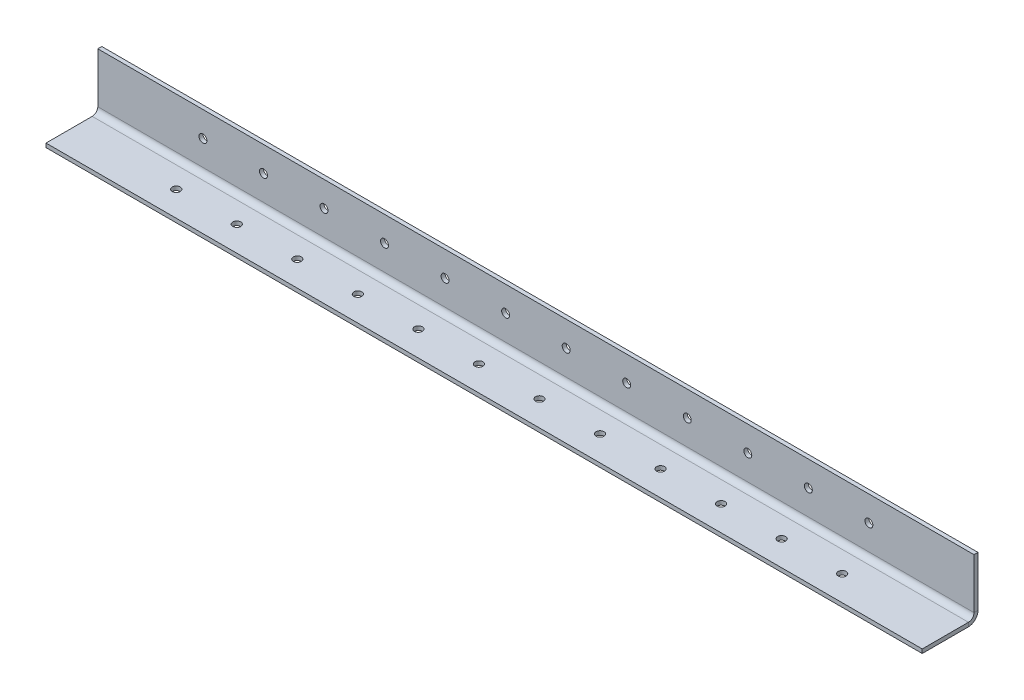
SolidWorks part; units mm, degrees
note: The reader was unsure of these and kept them because the rebuilt part matched: flange length of "Edge-Flange1".
material "Plain Carbon Steel"
ref_plane "Front Plane" through (0, 0, 0) normal (0, 0, 1) x (1, 0, 0)
ref_plane "Top Plane" through (0, 0, 0) normal (0, 1, 0) x (1, 0, 0)
ref_plane "Right Plane" through (0, 0, 0) normal (1, 0, 0) x (0, 0, -1)
sketch "Sketch1" plane through (0, 0, 0) normal (0, 0, 1) x (1, 0, 0)
  line L1 (-1100, -75) -> (1100, -75)
  line L2 (-1100, -75) -> (-1100, 75)
  line L3 (-1100, 75) -> (1100, 75)
  line L4 (1100, -75) -> (1100, 75)
  line L5 (-1100, -75) -> (1100, 75) construction
  line L6 (-1100, 75) -> (1100, -75) construction
  point P0 (0, 0)
  dimension "D1" = 2200
  dimension "D2" = 150
base flange "Base-Flange1" sketch "Sketch1" thickness 10 reverse thickness direction no parameters "D1"=3
edge flange "Edge-Flange1" sketch "Sketch10" flange angle 90 flange length 140 flange position material inside bend radius 14 thickness 10 relief rectangular parameters "D6"=10, "D8"=1
sketch "Sketch10" plane through (0, -75, 0) normal (0, -1, 0) x (1, 0, 0)
  line L0 (-1100, 0) -> (1100, 0) construction
  line L1 (-1100, 0) -> (1100, 0)
  line L2 (-1100, 0) -> (-1100, 130)
  line L3 (-1100, 130) -> (1100, 130)
  line L4 (1100, 130) -> (1100, 0)
bend "EdgeBend1" bend radius 14 bend angle 90 parameters "D5"=1
sketch "Sketch12" plane through (0, -75, 0) normal (0, -1, 0) x (-1, 0, 0)
  line L0 (1100, 0) -> (1100, -130) construction
  line L2 (-1100, -130) -> (1100, -130) construction
  circle A0 centre (836, -67) radius 10
  dimension "D1" = 20
  dimension "D2" = 264
  dimension "D3" = 63
extrude "Cut-Extrude1" cut sketch "Sketch12" against normal blind 10
sketch "Sketch13" plane through (0, 0, -10) normal (0, 0, -1) x (-1, 0, 0)
  line L3 (1100, 75) -> (1100, -51) construction
  circle A0 centre (836, 12) radius 10
  point P6 (1100, 12)
  dimension "D1" = 20
  dimension "D2" = 264
extrude "Cut-Extrude2" cut sketch "Sketch13" against normal blind 10
pattern_linear "LPattern1" count 12 spacing 152 along (1, 0, 0) of "Cut-Extrude1", "Cut-Extrude2"
sketch "Bend-Lines1" [suppressed] plane through (0, 0, 0) normal (0, 1, 0) x (1, 0, 0)
sketch "Bounding-Box1" [suppressed] plane through (0, 0, 0) normal (0, 1, 0) x (1, 0, 0)
sheet metal parameters "Sheet-Metal1" thickness 10 parameters "D1"=3
flat pattern "Flat-Pattern1" [suppressed]
sketch "Bend-Lines2" plane through (0, 0, 0) normal (0, 1, 0) x (1, 0, 0)
sketch3d "Bounding-Box2" [suppressed]
  line L0 (800, -100, 0) -> (-800, -100, 0) construction
  line L1 (800, 100, 0) -> (-800, 100, 0) construction
  line L2 (800, -100, 0) -> (800, 100, 0) construction
  line L3 (-800, -100, 0) -> (-800, 100, 0) construction
sheet metal parameters "Sheet-Metal2" thickness 10 parameters "D1"=3
flat pattern "Flat-Pattern1"
sketch "Bend-Lines2" plane through (0, 0, 0) normal (0, 0, 1) x (1, 0, 0)
  line L1 (-950, -65.9226) -> (950, -65.9226) construction
  line L3 (-950, -65.9226) -> (950, -65.9226) construction
sketch3d "Bounding-Box2" [suppressed]
  line L0 (-950, -206.8451, 0) -> (950, -206.8451, 0) construction
  line L1 (-950, 75, 0) -> (950, 75, 0) construction
  line L2 (-950, -206.8451, 0) -> (-950, 75, 0) construction
  line L3 (950, -206.8451, 0) -> (950, 75, 0) construction
bend of the flat pattern "Flatten-<EdgeBend1>1"
sheet metal parameters "Sheet-Metal3" thickness 10 parameters "D1"=3
flat pattern "Flat-Pattern1"
sketch "Bend-Lines2" plane through (0, 0, 0) normal (0, 0, 1) x (1, 0, 0)
  line L1 (-950, -65.9226) -> (950, -65.9226) construction
  line L3 (-950, -65.9226) -> (950, -65.9226) construction
sketch3d "Bounding-Box2" [suppressed]
  line L0 (-950, -206.8451, 0) -> (950, -206.8451, 0) construction
  line L1 (-950, 75, 0) -> (950, 75, 0) construction
  line L2 (-950, -206.8451, 0) -> (-950, 75, 0) construction
  line L3 (950, -206.8451, 0) -> (950, 75, 0) construction
bend of the flat pattern "Flatten-<EdgeBend1>1"
sheet metal parameters "Sheet-Metal4" thickness 10 parameters "D1"=3
flat pattern "Flat-Pattern1"
sketch "Bend-Lines2" plane through (0, 0, 0) normal (0, 0, 1) x (1, 0, 0)
  line L1 (-1100, -65.9226) -> (1100, -65.9226) construction
  line L3 (-1100, -65.9226) -> (1100, -65.9226) construction
sketch3d "Bounding-Box2" [suppressed]
  line L0 (-1100, -196.8451, 0) -> (1100, -196.8451, 0) construction
  line L1 (-1100, 75, 0) -> (1100, 75, 0) construction
  line L2 (-1100, -196.8451, 0) -> (-1100, 75, 0) construction
  line L3 (1100, -196.8451, 0) -> (1100, 75, 0) construction
bend of the flat pattern "Flatten-<EdgeBend1>1"
sheet metal parameters "Sheet-Metal5" thickness 10 parameters "D1"=3
flat pattern "Flat-Pattern1"
sketch "Bend-Lines2" plane through (0, 0, 0) normal (0, 0, 1) x (1, 0, 0)
  line L1 (-950, -65.9226) -> (950, -65.9226) construction
  line L3 (-950, -65.9226) -> (950, -65.9226) construction
sketch3d "Bounding-Box2" [suppressed]
  line L0 (-950, -206.8451, 0) -> (950, -206.8451, 0) construction
  line L1 (-950, 75, 0) -> (950, 75, 0) construction
  line L2 (-950, -206.8451, 0) -> (-950, 75, 0) construction
  line L3 (950, -206.8451, 0) -> (950, 75, 0) construction
bend of the flat pattern "Flatten-<EdgeBend1>1"
